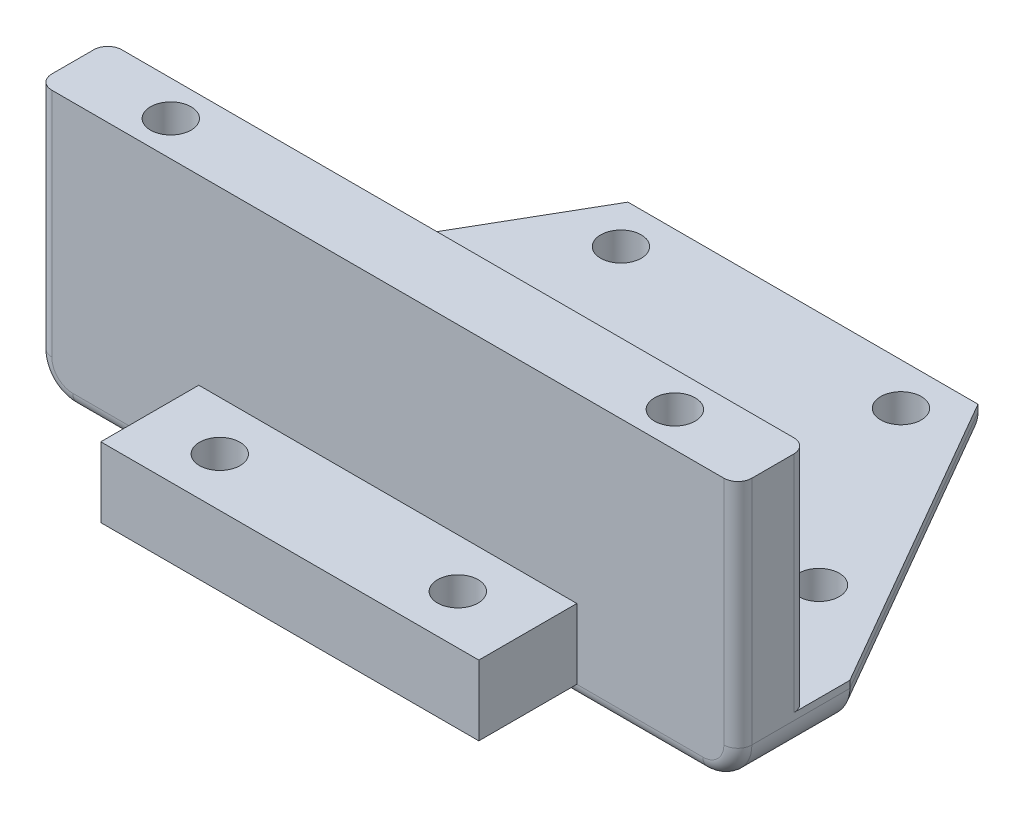
SolidWorks part; units mm, degrees
ref_plane "Спереди" through (0, 0, 0) normal (0, 0, 1) x (1, 0, 0)
ref_plane "Сверху" through (0, 0, 0) normal (0, 1, 0) x (1, 0, 0)
ref_plane "Справа" through (0, 0, 0) normal (1, 0, 0) x (0, 0, -1)
sketch "Эскиз1" plane through (0, 0, 0) normal (0, 1, 0) x (1, 0, 0)
  line L0 (-25, 0) -> (-12.5, 21.6506)
  line L1 (-12.5, 21.6506) -> (12.5, 21.6506)
  line L2 (12.5, 21.6506) -> (25, 0)
  line L3 (25, 0) -> (-25, 0)
  point P5 (0, 21.6506)
  dimension "D1" = 25
  dimension "D2" = 50
  dimension "D3" = 60
extrude "Бобышка-Вытянуть1" add sketch "Эскиз1" along normal blind 3
sketch "Эскиз2" plane through (0, 3, 0) normal (0, 1, 0) x (1, 0, 0)
  line L0 (0, -1000) -> (0, 49000) construction
  line L1 (-25, 0) -> (25, 0) construction
  line L2 (-10, 18.6506) -> (-18, 4.7942) construction
  line L3 (-12.5, 21.6506) -> (-25, 0) construction
  line L5 (12.5, 21.6506) -> (-12.5, 21.6506) construction
  line L6 (10, 18.6506) -> (18, 4.7942) construction
  line L7 (-1018, 4.7942) -> (48982, 4.7942) construction
  circle A0 centre (-10, 18.6506) radius 1.45
  circle A1 centre (-18, 4.7942) radius 1.45
  circle A2 centre (18, 4.7942) radius 1.45
  circle A3 centre (10, 18.6506) radius 1.45
  circle A4 centre (-6, 4.7942) radius 1.45
  circle A5 centre (6, 4.7942) radius 1.45
  point P5 (0, 0)
  dimension "D1" = 2.9
  dimension "D2" = 2.9
  dimension "D6" = 12
  dimension "D3" = 10
  dimension "D4" = 18
  dimension "D5" = 3
  dimension "D7" = 12
extrude "Вырез-Вытянуть1" cut sketch "Эскиз2" against normal blind 3
sketch "Эскиз3" plane through (0, 0, 0) normal (0, 0, 1) x (1, 0, 0)
  line L1 (25, 0) -> (-25, 0)
  line L2 (25, 0) -> (25, 3)
  line L3 (25, 3) -> (-25, 3)
  line L4 (-25, 0) -> (-25, 3)
extrude "Бобышка-Вытянуть2" add sketch "Эскиз3" along normal blind 8
sketch "Эскиз4" plane through (0, 3, 0) normal (0, 1, 0) x (1, 0, 0)
  line L1 (-25, -8) -> (25, -8)
  line L2 (-25, -8) -> (-25, -3)
  line L3 (-25, -3) -> (25, -3)
  line L4 (25, -8) -> (25, -3)
  dimension "D1" = 5
extrude "Бобышка-Вытянуть3" add sketch "Эскиз4" along normal blind 16
sketch "Эскиз6" plane through (0, 0, 8) normal (0, 0, 1) x (1, 0, 0)
  line L0 (-25, 0) -> (25, 0) construction
  line L1 (-13.5, 1) -> (13.5, 1)
  line L2 (-13.5, 1) -> (-13.5, 6)
  line L3 (-13.5, 6) -> (13.5, 6)
  line L4 (13.5, 1) -> (13.5, 6)
  point P6 (0, 1)
  dimension "D1" = 27
  dimension "D2" = 5
  dimension "D3" = 1
extrude "Бобышка-Вытянуть4" add sketch "Эскиз6" along normal blind 7
sketch "Эскиз7" plane through (0, 1, 0) normal (0, -1, 0) x (1, 0, 0)
  line L0 (-1013.5, 11.5) -> (48986.5, 11.5) construction
  line L1 (-13.5, 15) -> (-13.5, 8) construction
  line L2 (13.5, 15) -> (13.5, 8) construction
  circle A0 centre (-8.5, 11.5) radius 1.45
  circle A1 centre (8.5, 11.5) radius 1.45
  point P5 (-13.5, 11.5)
  dimension "D1" = 2.9
  dimension "D3" = 5
  dimension "D2" = 5
extrude "Вырез-Вытянуть2" cut sketch "Эскиз7" against normal blind 7
sketch "Эскиз8" plane through (0, 1, 0) normal (0, -1, 0) x (1, 0, 0)
  circle A0 centre (-8.5, 11.5) radius 3
  circle A1 centre (8.5, 11.5) radius 3
  dimension "D1" = 6
extrude "Вырез-Вытянуть3" cut sketch "Эскиз8" against normal blind 2
fillet "Скругление1" radius 1 5 edges at (-25, 9.5, 8) (25, 9.5, 8) (0, 0, 8) (25, 11, 3) (-25, 11, 3)
fillet "Скругление2" radius 2.5 7 edges at (24.7071, 0.2929, 7.7071) (-24.7071, 0.2929, 7.7071) (-25, 0, 3.5) (-18.75, 0, -10.8253) (0, 0, -21.6506) (18.75, 0, -10.8253) (25, 0, 3.5)
sketch "Эскиз9" plane through (0, 19, 0) normal (0, 1, 0) x (1, 0, 0)
  line L0 (-1022.9102, -5.5) -> (48977.0898, -5.5) construction
  line L1 (24, -3) -> (-24, -3) construction
  line L2 (-25, -4) -> (-25, -7) construction
  line L3 (25, -7) -> (25, -4) construction
  circle A0 centre (-18, -5.5) radius 1.45
  circle A1 centre (18, -5.5) radius 1.45
  point P8 (-19.3448, -5.5)
  point P9 (19.2897, -6.0015)
  point P10 (20.41, -5.5)
  dimension "D1" = 2.5
  dimension "D2" = 2.9
  dimension "D3" = 7
  dimension "D4" = 7
extrude "Вырез-Вытянуть4" cut sketch "Эскиз9" against normal blind 10
